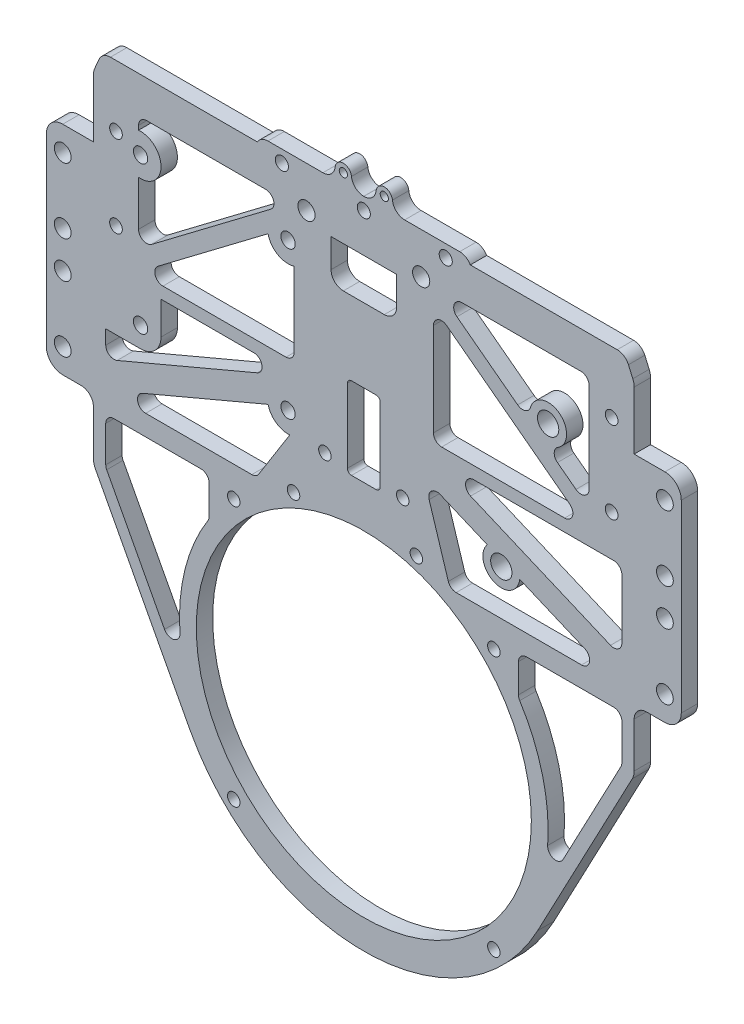
SolidWorks part; units mm, degrees
material "Thornel Mat VMA"
ref_plane "前视基准面" through (0, 0, 0) normal (0, 0, 1) x (1, 0, 0)
ref_plane "上视基准面" through (0, 0, 0) normal (0, 1, 0) x (1, 0, 0)
ref_plane "右视基准面" through (0, 0, 0) normal (1, 0, 0) x (0, 0, -1)
sketch "草图1" plane through (0, 0, 0) normal (0, 0, 1) x (1, 0, 0)
  line L0 (0, 0) -> (12.8351, 41.9818) construction
  line L1 (-48, 0) -> (48, 0) construction
  line L2 (-48, 0) -> (-48, 105.1) construction
  line L3 (-48, 105.1) -> (48, 105.1)
  line L4 (48, 0) -> (48, 105.1) construction
  line L5 (0, 0) -> (-17.1531, 40.4102) construction
  line L6 (0, 0) -> (0, 40.9) construction
  line L7 (-9.5, 52.6) -> (9.5, 52.6) construction
  line L8 (-42.4264, -22.4499) -> (-66, 22.1)
  line L9 (-14, 101.6) -> (14, 101.6) construction
  line L10 (-66, 22.1) -> (-66, 105.1)
  line L11 (0, 0) -> (0, 52.6) construction
  line L12 (0, 52.6) -> (0, 101.6) construction
  line L13 (-66, 105.1) -> (-48, 105.1)
  line L14 (48, 105.1) -> (66, 105.1)
  line L15 (66, 105.1) -> (66, 22.1)
  line L16 (66, 22.1) -> (42.4264, -22.4499)
  arc A0 (-42.4264, -22.4499) -> (42.4264, -22.4499) centre (0, 0) ccw
  circle A1 centre (0, 0) radius 40.9
  circle A2 centre (12.8351, 41.9818) radius 1.525
  circle A3 centre (-17.1531, 40.4102) radius 1.525
  circle A4 centre (0, 0) radius 44.9 construction
  circle A5 centre (-31.7491, 31.7491) radius 1.525
  circle A6 centre (31.7491, 31.7491) radius 1.525
  circle A7 centre (31.7491, -31.7491) radius 1.525
  circle A8 centre (-31.7491, -31.7491) radius 1.525
  circle A9 centre (-14, 101.6) radius 2.1
  circle A10 centre (14, 101.6) radius 2.1
  circle A11 centre (-9.5, 52.6) radius 1.525
  circle A12 centre (9.5, 52.6) radius 1.525
  point P24 (0, 0)
  dimension "D2" = 96
  dimension "D3" = 81.8
  dimension "D8" = 89.8
  dimension "D9" = 3.05
  dimension "D14" = 4.2
  dimension "D1" = 105.1
  dimension "D4" = 43.9
  dimension "D5" = 17
  dimension "D6" = 40
  dimension "D10" = 52.6
  dimension "D11" = 19
  dimension "D12" = 28
  dimension "D13" = 49
  dimension "D15" = 132
  dimension "D16" = 83
  dimension "D7" = 4
extrude "凸台-拉伸1" add sketch "草图1" along normal blind 4
sketch "草图3" plane through (0, 0, 4) normal (0, 0, 1) x (1, 0, 0)
  line L0 (-66, 105.1) -> (-42, 160.1)
  line L1 (-42, 160.1) -> (-22, 160.1)
  line L2 (-22, 160.1) -> (-22, 105.1)
  line L3 (66, 105.1) -> (-66, 105.1) construction
  line L4 (-22, 105.1) -> (-66, 105.1)
  line L5 (0, 105.1) -> (0, 160.1) construction
  line L6 (22, 160.1) -> (22, 105.1)
  line L7 (42, 160.1) -> (22, 160.1)
  line L8 (66, 105.1) -> (42, 160.1)
  line L9 (22, 105.1) -> (66, 105.1)
  dimension "D1" = 44
  dimension "D2" = 55
  dimension "D3" = 20
extrude "凸台-拉伸2" add sketch "草图3" against normal up to surface (4 mm away) up to face at (0, 30.6583, 0)
sketch "草图4" plane through (0, 0, 4) normal (0, 0, 1) x (1, 0, 0)
  line L0 (-66, 105.1) -> (-60.5, 105.1) construction
  line L1 (-60.5, 105.1) -> (-60.5, 95.1) construction
  line L2 (-60.5, 95.1) -> (-60.5, 75.1) construction
  line L3 (-42, 160.1) -> (-38.3338, 158.5002) construction
  line L4 (-38.3338, 158.5002) -> (-42.3333, 149.3348) construction
  line L5 (-42.3333, 149.3348) -> (-50.3322, 131.004) construction
  line L7 (-42, 160.1) -> (-66, 105.1) construction
  line L8 (0, 105.1) -> (0, 145.1) construction
  line L9 (22, 105.1) -> (-22, 105.1) construction
  circle A0 centre (-60.5, 95.1) radius 1.55
  circle A1 centre (-60.5, 75.1) radius 1.55
  circle A2 centre (-42.3333, 149.3348) radius 1.55
  circle A3 centre (-50.3322, 131.004) radius 1.55
  circle A4 centre (60.5, 75.1) radius 1.55
  circle A5 centre (60.5, 95.1) radius 1.55
  circle A6 centre (50.3322, 131.004) radius 1.55
  circle A7 centre (42.3333, 149.3348) radius 1.55
  dimension "D5" = 3.1
  dimension "D1" = 5.5
  dimension "D2" = 10
  dimension "D3" = 20
  dimension "D4" = 10
  dimension "D6" = 4
extrude "切除-拉伸2" cut sketch "草图4" against normal blind 10
sketch "草图5" plane through (0, 0, 4) normal (0, 0, 1) x (1, 0, 0)
  line L0 (22, 105.1) -> (-22, 105.1) construction
  line L1 (-8, 105.1) -> (8, 105.1)
  line L2 (-8, 105.1) -> (-8, 92.1)
  line L3 (-5, 89.1) -> (5, 89.1)
  line L4 (8, 105.1) -> (8, 92.1)
  arc A0 (-8, 92.1) -> (-5, 89.1) centre (-5, 92.1) ccw
  arc A1 (5, 89.1) -> (8, 92.1) centre (5, 92.1) ccw
  point P6 (0, 105.1)
  point P11 (8, 89.1)
  dimension "D3" = 3
  dimension "D1" = 16
  dimension "D2" = 16
extrude "切除-拉伸3" cut sketch "草图5" against normal blind 10
sketch "草图6" plane through (0, 0, 4) normal (0, 0, 1) x (1, 0, 0)
  line L0 (-66, 105.1) -> (-66, 22.1) construction
  line L1 (-66, 74.1) -> (-73.5, 74.1)
  line L2 (-66, 74.1) -> (-66, 37.1)
  line L3 (-66, 37.1) -> (-73.5, 37.1)
  line L4 (-77.5, 70.1) -> (-77.5, 41.1)
  line L5 (0, 0) -> (0, 40.9) construction
  line L6 (-73.5, 74.1) -> (-73.5, 68.1) construction
  line L7 (-73.5, 68.1) -> (-73.5, 43.1) construction
  line L8 (-73.5, 43.1) -> (-73.5, 37.1) construction
  line L9 (66, 37.1) -> (73.5, 37.1)
  line L10 (77.5, 70.1) -> (77.5, 41.1)
  line L11 (66, 74.1) -> (73.5, 74.1)
  line L12 (66, 74.1) -> (66, 37.1)
  circle A0 centre (0, 0) radius 40.9 construction
  circle A1 centre (-73.5, 68.1) radius 2.05
  circle A2 centre (-73.5, 43.1) radius 2.05
  arc A5 (-73.5, 74.1) -> (-77.5, 70.1) centre (-73.5, 70.1) ccw
  arc A6 (-73.5, 37.1) -> (-77.5, 41.1) centre (-73.5, 41.1) cw
  circle A7 centre (73.5, 43.1) radius 2.05
  circle A8 centre (73.5, 68.1) radius 2.05
  arc A9 (73.5, 37.1) -> (77.5, 41.1) centre (73.5, 41.1) ccw
  arc A10 (73.5, 74.1) -> (77.5, 70.1) centre (73.5, 70.1) cw
  point P25 (-73.5, 55.6)
  point P28 (-77.5, 74.1)
  point P31 (-77.5, 37.1)
  dimension "D5" = 4.1
  dimension "D7" = 4
  dimension "D1" = 11.5
  dimension "D2" = 4
  dimension "D3" = 6
  dimension "D4" = 25
  dimension "D6" = 55.6
extrude "凸台-拉伸3" add sketch "草图6" against normal up to surface (4 mm away) up to face at (0, 89.2171, 0)
fillet "圆角1" radius 3 6 edges at (-8, 105.1, 2) (8, 105.1, 2) (66, 37.1, 2) (66, 74.1, 2) (-66, 74.1, 2) (-66, 37.1, 2)
fillet "圆角2" radius 2 2 edges at (-22, 105.1, 2) (22, 105.1, 2)
fillet "圆角3" radius 4 8 edges at (66, 22.1, 2) (-66, 22.1, 2) (-66, 105.1, 2) (-42, 160.1, 2) (-22, 160.1, 2) (22, 160.1, 2) (42, 160.1, 2) (66, 105.1, 2)
sketch "草图8" plane through (0, 0, 4) normal (0, 0, 1) x (1, 0, 0)
  line L0 (0, 51.1) -> (0, 0) construction
  line L1 (-3, 51.1) -> (3, 51.1)
  line L2 (-4, 52.1) -> (-4, 70.1)
  line L3 (-3, 71.1) -> (3, 71.1)
  line L4 (4, 52.1) -> (4, 70.1)
  arc A0 (3, 51.1) -> (4, 52.1) centre (3, 52.1) ccw
  arc A1 (-4, 70.1) -> (-3, 71.1) centre (-3, 70.1) cw
  arc A2 (3, 71.1) -> (4, 70.1) centre (3, 70.1) cw
  arc A3 (-3, 51.1) -> (-4, 52.1) centre (-3, 52.1) cw
  point P9 (4, 51.1)
  point P14 (4, 71.1)
  point P17 (-4, 51.1)
  dimension "D3" = 1
  dimension "D1" = 20
  dimension "D2" = 8
  dimension "D4" = 51.1
extrude "切除-拉伸5" cut sketch "草图8" against normal blind 10
sketch "草图9" plane through (0, 0, 4) normal (0, 0, 1) x (1, 0, 0)
  line L0 (-53.257, 114.2998) -> (-37.548, 150.2998)
  line L1 (-34.7983, 152.1) -> (-33, 152.1)
  line L2 (-30, 149.1) -> (-30, 113.1)
  line L3 (-33, 110.1) -> (-50.5074, 110.1)
  line L4 (0, 0) -> (0, 89.1) construction
  line L5 (-5, 89.1) -> (5, 89.1) construction
  line L6 (-43.0474, 157.6998) -> (-65.6662, 105.8651) construction
  line L7 (-26, 160.1) -> (-39.3812, 160.1) construction
  line L8 (-22, 107.1) -> (-22, 156.1) construction
  line L9 (-11, 105.1) -> (-20, 105.1) construction
  line L10 (33, 110.1) -> (50.5074, 110.1)
  line L11 (30, 149.1) -> (30, 113.1)
  line L12 (34.7983, 152.1) -> (33, 152.1)
  line L13 (53.257, 114.2998) -> (37.548, 150.2998)
  arc A0 (-53.257, 114.2998) -> (-50.5074, 110.1) centre (-50.5074, 113.1) ccw
  arc A1 (-30, 113.1) -> (-33, 110.1) centre (-33, 113.1) cw
  arc A2 (-33, 152.1) -> (-30, 149.1) centre (-33, 149.1) cw
  arc A3 (-37.548, 150.2998) -> (-34.7983, 152.1) centre (-34.7983, 149.1) cw
  arc A4 (37.548, 150.2998) -> (34.7983, 152.1) centre (34.7983, 149.1) ccw
  arc A5 (33, 152.1) -> (30, 149.1) centre (33, 149.1) ccw
  arc A6 (30, 113.1) -> (33, 110.1) centre (33, 113.1) ccw
  arc A7 (53.257, 114.2998) -> (50.5074, 110.1) centre (50.5074, 113.1) cw
  dimension "D5" = 3
  dimension "D1" = 8
  dimension "D2" = 8
  dimension "D3" = 8
  dimension "D4" = 5
extrude "切除-拉伸6" cut sketch "草图9" against normal through all
sketch "草图10" plane through (0, 0, 4) normal (0, 0, 1) x (1, 0, 0)
  line L0 (66, 77.1) -> (66, 104.2653) construction
  line L1 (13, 107.1) -> (49, 107.1) construction
  line L2 (13, 107.1) -> (13, 71.1) construction
  line L3 (13, 71.1) -> (49, 71.1) construction
  line L4 (49, 107.1) -> (49, 71.1) construction
  line L5 (39.3812, 160.1) -> (26, 160.1) construction
  line L6 (0, 0) -> (0, 40.9) construction
  line L7 (-49, 107.1) -> (-49, 71.1) construction
  line L8 (-13, 71.1) -> (-49, 71.1) construction
  line L9 (-13, 107.1) -> (-13, 71.1) construction
  line L10 (-13, 107.1) -> (-49, 107.1) construction
  line L11 (48.6489, -4.2763) -> (62.7678, 22.4059)
  line L12 (63, 23.3413) -> (63, 32.1)
  line L13 (61, 34.1) -> (39.7491, 34.1)
  line L14 (37.7491, 32.1) -> (37.7491, 25.0801)
  line L15 (42.4264, -22.4499) -> (65.5355, 21.2222) construction
  line L16 (66, 23.0931) -> (66, 34.1) construction
  line L17 (69, 37.1) -> (73.5, 37.1) construction
  line L18 (-61, 34.1) -> (-39.7491, 34.1)
  line L19 (-63, 23.3413) -> (-63, 32.1)
  line L20 (-48.6489, -4.2763) -> (-62.7678, 22.4059)
  line L21 (-37.7491, 32.1) -> (-37.7491, 25.0801)
  line L22 (17, 70.1) -> (17, 92.8061)
  line L23 (20.206, 94.4016) -> (50.2436, 71.6955)
  line L24 (49.0376, 68.1) -> (19, 68.1)
  line L25 (23.9405, 101.1) -> (53, 101.1)
  line L26 (55, 99.1) -> (55, 77.1332)
  line L27 (51.794, 75.5378) -> (22.7345, 97.5045)
  line L28 (20, 105.1) -> (11, 105.1) construction
  line L29 (18.631, 57.8877) -> (53.9274, 42.9417)
  line L30 (53.1476, 39.1) -> (22.5456, 39.1)
  line L31 (20.6375, 40.5007) -> (15.9431, 55.4467)
  line L32 (26.8383, 65.1) -> (61, 65.1)
  line L33 (63, 63.1) -> (63, 48.6345)
  line L34 (60.2202, 46.7928) -> (26.0585, 61.2583)
  line L35 (9.5, 52.6) -> (12.8351, 41.9818) construction
  line L36 (14.6464, 59.5749) -> (16.9859, 65.1) construction
  line L37 (-55, 99.1) -> (-55, 77.1332)
  line L38 (-23.9405, 101.1) -> (-53, 101.1)
  line L39 (-51.794, 75.5378) -> (-22.7345, 97.5045)
  line L40 (-20.206, 94.4016) -> (-50.2436, 71.6955)
  line L41 (-17, 70.1) -> (-17, 92.8061)
  line L42 (-49.0376, 68.1) -> (-19, 68.1)
  line L43 (-63, 63.1) -> (-63, 48.6345)
  line L44 (-26.8383, 65.1) -> (-61, 65.1)
  line L45 (-60.2202, 46.7928) -> (-26.0585, 61.2583)
  line L49 (-54.0396, 42.9417) -> (-18.7431, 57.8877)
  line L50 (-16.2694, 54.9825) -> (-25.6529, 40.0366)
  line L51 (-27.3467, 39.1) -> (-53.2597, 39.1)
  line L52 (-17.1531, 40.4102) -> (-9.5, 52.6) construction
  circle A3 centre (0, 0) radius 40.9 construction
  arc A7 (38.0576, 24.0128) -> (44.8862, -3.1987) centre (0, 0) cw
  circle A8 centre (31.7491, 31.7491) radius 1.525 construction
  arc A9 (44.8862, -3.1987) -> (48.6489, -4.2763) centre (46.8811, -3.3409) ccw
  arc A10 (62.7678, 22.4059) -> (63, 23.3413) centre (61, 23.3413) ccw
  arc A11 (63, 32.1) -> (61, 34.1) centre (61, 32.1) ccw
  arc A12 (38.0576, 24.0128) -> (37.7491, 25.0801) centre (39.7491, 25.0801) cw
  arc A13 (39.7491, 34.1) -> (37.7491, 32.1) centre (39.7491, 32.1) ccw
  arc A14 (-63, 32.1) -> (-61, 34.1) centre (-61, 32.1) cw
  arc A15 (-62.7678, 22.4059) -> (-63, 23.3413) centre (-61, 23.3413) cw
  arc A16 (-44.8862, -3.1987) -> (-48.6489, -4.2763) centre (-46.8811, -3.3409) cw
  arc A17 (-38.0576, 24.0128) -> (-44.8862, -3.1987) centre (0, 0) ccw
  arc A18 (-38.0576, 24.0128) -> (-37.7491, 25.0801) centre (-39.7491, 25.0801) ccw
  arc A19 (-39.7491, 34.1) -> (-37.7491, 32.1) centre (-39.7491, 32.1) cw
  circle A20 centre (14, 101.6) radius 2.1 construction
  arc A21 (53, 101.1) -> (55, 99.1) centre (53, 99.1) cw
  arc A22 (55, 77.1332) -> (51.794, 75.5378) centre (53, 77.1332) cw
  arc A23 (50.2436, 71.6955) -> (49.0376, 68.1) centre (49.0376, 70.1) cw
  arc A24 (17, 70.1) -> (19, 68.1) centre (19, 70.1) ccw
  arc A25 (17, 92.8061) -> (20.206, 94.4016) centre (19, 92.8061) cw
  arc A26 (23.9405, 101.1) -> (22.7345, 97.5045) centre (23.9405, 99.1) ccw
  arc A27 (61, 65.1) -> (63, 63.1) centre (61, 63.1) cw
  arc A28 (63, 48.6345) -> (60.2202, 46.7928) centre (61, 48.6345) cw
  arc A29 (53.9274, 42.9417) -> (53.1476, 39.1) centre (53.1476, 41.1) cw
  arc A30 (22.5456, 39.1) -> (20.6375, 40.5007) centre (22.5456, 41.1) cw
  arc A31 (18.631, 57.8877) -> (15.9431, 55.4467) centre (17.8511, 56.046) ccw
  arc A32 (26.8383, 65.1) -> (26.0585, 61.2583) centre (26.8383, 63.1) ccw
  arc A33 (-53, 101.1) -> (-55, 99.1) centre (-53, 99.1) ccw
  arc A34 (-55, 77.1332) -> (-51.794, 75.5378) centre (-53, 77.1332) ccw
  arc A35 (-23.9405, 101.1) -> (-22.7345, 97.5045) centre (-23.9405, 99.1) cw
  arc A36 (-17, 92.8061) -> (-20.206, 94.4016) centre (-19, 92.8061) ccw
  arc A37 (-50.2436, 71.6955) -> (-49.0376, 68.1) centre (-49.0376, 70.1) ccw
  arc A38 (-17, 70.1) -> (-19, 68.1) centre (-19, 70.1) cw
  arc A39 (-61, 65.1) -> (-63, 63.1) centre (-61, 63.1) ccw
  arc A40 (-63, 48.6345) -> (-60.2202, 46.7928) centre (-61, 48.6345) ccw
  arc A41 (-26.8383, 65.1) -> (-26.0585, 61.2583) centre (-26.8383, 63.1) cw
  arc A45 (-54.0396, 42.9417) -> (-53.2597, 39.1) centre (-53.2597, 41.1) ccw
  arc A46 (-25.6529, 40.0366) -> (-27.3467, 39.1) centre (-27.3467, 41.1) cw
  arc A47 (-18.7431, 57.8877) -> (-16.2694, 54.9825) centre (-17.9633, 56.046) cw
  point P83 (55, 68.1)
  point P96 (63, 39.1)
  dimension "D4" = 3
  dimension "D7" = 45
  dimension "D12" = 2
  dimension "D19" = 2
  dimension "D24" = 2
  dimension "D25" = 2
  dimension "D1" = 36
  dimension "D2" = 36
  dimension "D3" = 17
  dimension "D6" = 53
  dimension "D8" = 6
  dimension "D9" = 3
  dimension "D10" = 3
  dimension "D11" = 3
  dimension "D13" = 11
  dimension "D14" = 4
  dimension "D15" = 3
  dimension "D16" = 2
  dimension "D17" = 2
  dimension "D20" = 5
  dimension "D21" = 6
  dimension "D22" = 6
  dimension "D23" = 7
  dimension "D26" = 7
extrude "切除-拉伸7" cut sketch "草图10" against normal through all
sketch "草图11" plane through (0, 0, 0) normal (0, 0, 1) x (1, 0, 0)
  line L1 (-66, 90.1) -> (-73.5, 90.1)
  line L2 (-66, 90.1) -> (-66, 53.1)
  line L3 (-66, 53.1) -> (-73.5, 53.1)
  line L4 (-77.5, 86.1) -> (-77.5, 57.1)
  line L5 (0, 0) -> (0, 40.9) construction
  line L6 (-73.5, 90.1) -> (-73.5, 84.1) construction
  line L7 (-73.5, 84.1) -> (-73.5, 59.1) construction
  line L8 (-73.5, 59.1) -> (-73.5, 53.1) construction
  line L9 (66, 53.1) -> (73.5, 53.1)
  line L10 (77.5, 86.1) -> (77.5, 57.1)
  line L11 (66, 90.1) -> (73.5, 90.1)
  line L12 (66, 90.1) -> (66, 53.1)
  line L13 (-66, 34.1) -> (-66, 23.0931) construction
  circle A1 centre (-73.5, 84.1) radius 2.05
  circle A2 centre (-73.5, 59.1) radius 2.05
  arc A5 (-73.5, 90.1) -> (-77.5, 86.1) centre (-73.5, 86.1) ccw
  arc A6 (-73.5, 53.1) -> (-77.5, 57.1) centre (-73.5, 57.1) cw
  circle A7 centre (73.5, 59.1) radius 2.05
  circle A8 centre (73.5, 84.1) radius 2.05
  arc A9 (73.5, 53.1) -> (77.5, 57.1) centre (73.5, 57.1) ccw
  arc A10 (73.5, 90.1) -> (77.5, 86.1) centre (73.5, 86.1) cw
  circle A11 centre (0, 0) radius 40.9 construction
  circle A13 centre (-73.5, 68.1) radius 2.05 construction
  circle A14 centre (73.5, 68.1) radius 2.05 construction
  circle A15 centre (73.5, 68.1) radius 2.05
  circle A16 centre (-73.5, 68.1) radius 2.05
  point P28 (-77.5, 90.1)
  point P31 (-77.5, 53.1)
  dimension "D5" = 4.1
  dimension "D7" = 4
  dimension "D1" = 11.5
  dimension "D2" = 4
  dimension "D3" = 6
  dimension "D4" = 25
  dimension "D6" = 16
extrude "凸台-拉伸4" add sketch "草图11" along normal up to surface (4 mm away) contours A6 L3 L2 L1 A5 L4 A2 A1 | A10 L11 L12 L9 A9 L10 A7 A8 region at (-71.4791, 71.7219, 0) region at (71.4791, 71.7219, 0) up to face at (30.8987, 45.8675, 4)
extrude "切除-拉伸9" cut sketch "草图11<2>" along normal blind 10 contours A2 | A7 region at (-73.5, 59.1, 0)
sketch "草图11<2>" plane through (0, 0, 0) normal (0, 0, 1) x (1, 0, 0) same geometry as "草图11"
sketch "草图12" plane through (0, 0, 4) normal (0, 0, 1) x (1, 0, 0)
  line L0 (-11, 105.1) -> (-20, 105.1) construction
  line L1 (-26, 160.1) -> (26, 160.1)
  line L2 (-26, 160.1) -> (-26, 105.1)
  line L3 (-26, 105.1) -> (26, 105.1)
  line L4 (26, 160.1) -> (26, 105.1)
extrude "切除-拉伸10" cut sketch "草图12" against normal through all
sketch "草图13" plane through (0, 0, 4) normal (0, 0, 1) x (1, 0, 0)
  line L1 (-26, 105.1) -> (-34, 105.1)
  line L2 (-26, 105.1) -> (-26, 155.1)
  line L3 (-26, 155.1) -> (-34, 155.1)
  line L4 (-34, 105.1) -> (-34, 155.1)
  line L5 (26, 105.1) -> (34, 105.1)
  line L6 (26, 105.1) -> (26, 155.1)
  line L7 (26, 155.1) -> (34, 155.1)
  line L8 (34, 105.1) -> (34, 155.1)
  dimension "D1" = 50
  dimension "D2" = 8
extrude "凸台-拉伸5" add sketch "草图13" against normal up to surface (4 mm away) up to face at (71.45, 59.1, 0)
sketch "草图14" plane through (0, 0, 0) normal (0, 0, -1) x (-1, 0, 0)
  line L0 (-31, 137.1) -> (-31, 117.1) construction
  line L1 (0, 0) -> (0, 89.1) construction
  line L2 (5, 89.1) -> (-5, 89.1) construction
  line L3 (31, 137.1) -> (31, 117.1) construction
  line L8 (-34, 152.1) -> (-34, 110.1) construction
  line L9 (-34, 110.1) -> (-50.5074, 110.1) construction
  circle A0 centre (-31, 137.1) radius 1.5
  circle A1 centre (-31, 117.1) radius 1.5
  circle A2 centre (31, 117.1) radius 1.5
  circle A3 centre (31, 137.1) radius 1.5
  dimension "D1" = 20
  dimension "D4" = 7
  dimension "D2" = 3
  dimension "D3" = 3
extrude "切除-拉伸11" cut sketch "草图14" against normal through all
sketch "草图15" plane through (0, 0, 4) normal (0, 0, 1) x (1, 0, 0)
  line L0 (45, 86.04) -> (45, 50.1) construction
  line L1 (45, 50.1) -> (33.57, 50.1) construction
  line L4 (66, 90.1) -> (66, 104.2653) construction
  circle A0 centre (45, 86.04) radius 2.6
  circle A1 centre (33.57, 50.1) radius 2.6
  circle A2 centre (45, 86.04) radius 4.5
  circle A6 centre (33.57, 50.1) radius 4.5
  circle A7 centre (14, 101.6) radius 2.1 construction
  dimension "D3" = 5.2
  dimension "D6" = 9
  dimension "D5" = 51.5
  dimension "D1" = 11.43
  dimension "D2" = 35.94
  dimension "D4" = 21
extrude "凸台-拉伸6" add sketch "草图15" against normal up to surface (4 mm away) up to face at (-29.5, 137.1, 0)
extrude "切除-拉伸12" cut sketch "草图15<2>" against normal through all contours A0 | A1 region at (45, 86.04, 4) region at (33.57, 50.1, 4)
sketch "草图15<2>" plane through (0, 0, 4) normal (0, 0, 1) x (1, 0, 0) same geometry as "草图15"
sketch "草图16" plane through (0, 0, 4) normal (0, 0, 1) x (1, 0, 0)
  line L0 (-54.5, 52.1) -> (-63, 52.1)
  line L1 (-54.5, 93.1) -> (-18.5, 93.1) construction
  line L2 (-54.5, 93.1) -> (-54.5, 57.1) construction
  line L3 (-54.5, 57.1) -> (-18.5, 57.1) construction
  line L4 (-18.5, 93.1) -> (-18.5, 57.1) construction
  line L5 (-63, 63.1) -> (-63, 48.6345) construction
  line L6 (-49.5, 57.1) -> (-49.5, 65.1)
  line L7 (-26.8383, 65.1) -> (-61, 65.1) construction
  line L8 (-63, 63.1) -> (-63, 52.1)
  line L9 (-49.5, 65.1) -> (-61, 65.1)
  circle A0 centre (-54.5, 93.1) radius 1.75
  circle A1 centre (-18.5, 93.1) radius 1.75
  circle A2 centre (-54.5, 57.1) radius 1.75
  circle A3 centre (-18.5, 57.1) radius 1.75
  circle A4 centre (-60.5, 95.1) radius 1.55 construction
  arc A5 (-59.4206, 93.9876) -> (-58.969, 95.3422) centre (-54.5, 93.1) ccw
  circle A6 centre (-18.5, 93.1) radius 5
  circle A7 centre (-18.5, 57.1) radius 5
  arc A8 (-54.5, 52.1) -> (-49.5, 57.1) centre (-54.5, 57.1) ccw
  arc A9 (-61, 65.1) -> (-63, 63.1) centre (-61, 63.1) ccw construction
  arc A10 (-61, 65.1) -> (-63, 63.1) centre (-61, 63.1) ccw
  arc A11 (-59.4206, 93.9876) -> (-58.969, 95.3422) centre (-60.5, 95.1) ccw
  dimension "D1" = 3.5
  dimension "D6" = 10
  dimension "D2" = 36
  dimension "D3" = 36
  dimension "D4" = 2
  dimension "D5" = 6
extrude "凸台-拉伸7" add sketch "草图16" against normal up to surface (4 mm away) up to face at (-29.5, 137.1, 0)
extrude "切除-拉伸13" cut sketch "草图16<2>" against normal through all contours A0 | A1 | A3 | A2 region at (-54.5, 93.1, 4) region at (-18.5, 93.1, 4) region at (-54.5, 57.1, 4) region at (-18.5, 57.1, 4)
sketch "草图16<2>" plane through (0, 0, 4) normal (0, 0, 1) x (1, 0, 0) same geometry as "草图16"
sketch "草图17" plane through (0, 0, 4) normal (0, 0, 1) x (1, 0, 0)
  line L0 (-26, 160.1) -> (-26, 105.1) construction
  line L1 (-26, 110.1) -> (-66, 110.1)
  line L2 (-26, 110.1) -> (-26, 160.1)
  line L3 (-26, 160.1) -> (-66, 160.1)
  line L4 (-66, 110.1) -> (-66, 160.1)
  line L5 (26, 110.1) -> (66, 110.1)
  line L6 (26, 110.1) -> (26, 160.1)
  line L7 (26, 160.1) -> (66, 160.1)
  line L8 (66, 110.1) -> (66, 160.1)
  line L9 (26, 105.1) -> (26, 160.1) construction
  line L10 (-66, 104.2653) -> (-66, 90.1) construction
  line L11 (66, 90.1) -> (66, 104.2653) construction
extrude "切除-拉伸15" cut sketch "草图17" against normal through all
sketch "草图18" plane through (0, 0, 4) normal (0, 0, 1) x (1, 0, 0)
  line L0 (26, 105.1) -> (26, 110.1) construction
  line L1 (26, 105.1) -> (11, 105.1) construction
  line L2 (8, 92.1) -> (8, 102.1) construction
  line L3 (-8, 102.1) -> (-8, 92.1) construction
  line L4 (-11, 105.1) -> (-26, 105.1) construction
  line L5 (-26, 110.1) -> (-26, 105.1) construction
  line L6 (26, 105.1) -> (26, 111.6)
  line L7 (26, 105.1) -> (11, 105.1)
  line L8 (8, 99.1) -> (8, 102.1)
  line L9 (-8, 102.1) -> (-8, 99.1)
  line L10 (-11, 105.1) -> (-26, 105.1)
  line L11 (-26, 111.6) -> (-26, 105.1)
  line L12 (-8, 99.1) -> (8, 99.1)
  line L13 (-26, 111.6) -> (-7, 111.6)
  line L14 (-5, 89.1) -> (5, 89.1) construction
  line L19 (-63.8182, 110.1) -> (-26, 110.1) construction
  line L20 (0, 108.6) -> (20, 108.6) construction
  line L21 (0, 108.6) -> (0, 111.6) construction
  line L22 (-5, 114.1) -> (5, 114.1) construction
  line L23 (-7, 114.1) -> (-7, 111.6)
  line L24 (-3, 114.1) -> (-3, 111.6)
  line L25 (3, 114.1) -> (3, 111.6)
  line L26 (7, 114.1) -> (7, 111.6)
  line L27 (-3, 111.6) -> (3, 111.6)
  line L28 (7, 111.6) -> (26, 111.6)
  arc A0 (11, 105.1) -> (8, 102.1) centre (11, 102.1) ccw construction
  arc A1 (-8, 102.1) -> (-11, 105.1) centre (-11, 102.1) ccw construction
  arc A2 (11, 105.1) -> (8, 102.1) centre (11, 102.1) ccw
  arc A3 (-8, 102.1) -> (-11, 105.1) centre (-11, 102.1) ccw
  circle A4 centre (0, 108.6) radius 1.6
  circle A5 centre (20, 108.6) radius 1.6
  circle A6 centre (-20, 108.6) radius 1.6
  circle A7 centre (-5, 114.1) radius 1
  circle A8 centre (5, 114.1) radius 1
  arc A9 (-3, 114.1) -> (-7, 114.1) centre (-5, 114.1) ccw
  arc A10 (7, 114.1) -> (3, 114.1) centre (5, 114.1) ccw
  point P27 (0, 99.1)
  point P34 (0, 114.1)
  dimension "D4" = 3.2
  dimension "D6" = 4
  dimension "D8" = 2
  dimension "D9" = 2.5
  dimension "D1" = 10
  dimension "D2" = 1.5
  dimension "D3" = 3
  dimension "D5" = 20
  dimension "D10" = 10
extrude "凸台-拉伸8" add sketch "草图18" against normal up to surface (4 mm away) up to face at (-45.698, 92.1913, 0)
fillet "圆角4" radius 2 2 edges at (41.3122, 83.4612, 2) (43.5247, 81.7887, 2)
fillet "圆角5" radius 3 8 edges at (63.8182, 110.1, 2) (-63.8182, 110.1, 2) (-26, 111.6, 2) (26, 111.6, 2) (7, 111.6, 2) (3, 111.6, 2) (-3, 111.6, 2) (-7, 111.6, 2)
